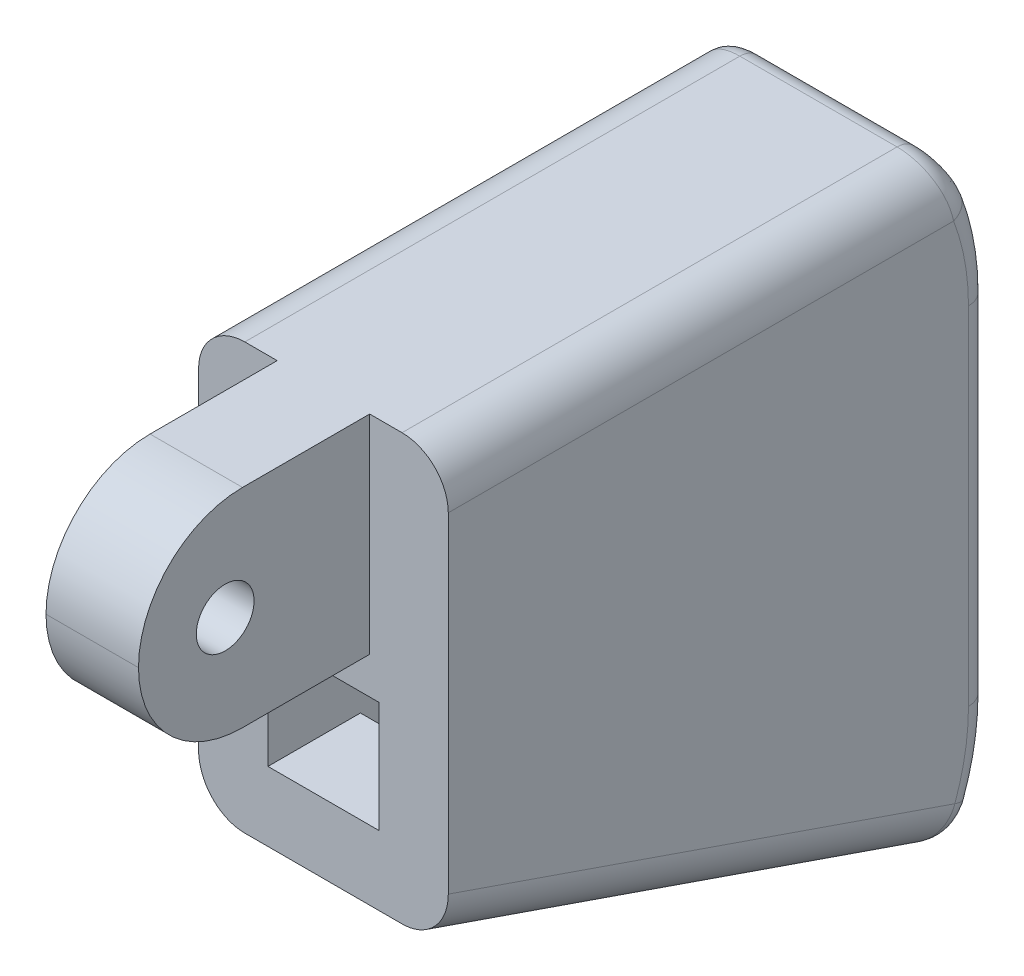
SolidWorks part; units mm, degrees
ref_plane "Front Plane" through (0, 0, 0) normal (0, 0, 1) x (1, 0, 0)
ref_plane "Top Plane" through (0, 0, 0) normal (0, 1, 0) x (1, 0, 0)
ref_plane "Right Plane" through (0, 0, 0) normal (1, 0, 0) x (0, 0, -1)
sketch "Sketch1" plane through (0, 0, 0) normal (0, 0, 1) x (1, 0, 0)
  line L1 (-2.4, -10) -> (2.4, -10)
  line L2 (-2.4, -10) -> (-2.4, 10)
  line L3 (-2.4, 10) -> (2.4, 10)
  line L4 (2.4, -10) -> (2.4, 10)
  line L5 (-2.4, -10) -> (2.4, 10) construction
  line L6 (-2.4, 10) -> (2.4, -10) construction
  line L7 (-5.4, -13) -> (5.4, -13)
  line L8 (-5.4, -13) -> (-5.4, 13)
  line L9 (-5.4, 13) -> (5.4, 13)
  line L10 (5.4, -13) -> (5.4, 13)
  line L11 (-5.4, -13) -> (5.4, 13) construction
  line L12 (-5.4, 13) -> (5.4, -13) construction
  line L13 (-2.4, 2.4) -> (2.4, 2.4)
  line L14 (-2.4, 2.4) -> (-2.4, -2.4)
  line L15 (-2.4, -2.4) -> (2.4, -2.4)
  line L16 (2.4, 2.4) -> (2.4, -2.4)
  line L17 (-2.4, 2.4) -> (2.4, -2.4) construction
  line L18 (-2.4, -2.4) -> (2.4, 2.4) construction
  point P0 (0, 0)
  point P6 (0, 0)
  point P11 (0, 0)
  dimension "D1" = 4.8
  dimension "D2" = 20
  dimension "D3" = 26
  dimension "D4" = 10.8
  dimension "D5" = 4.8
extrude "Boss-Extrude1" add sketch "Sketch1" along normal blind 18 contours L7 L10 L9 L8 L4 L1 L2 L3 region at (-5.1185, 0, 0)
sketch "Sketch2" plane through (0, 0, 18) normal (0, 0, 1) x (1, 0, 0)
  line L0 (2.4, -10) -> (2.4, 10) construction
  line L1 (-2.4, 2.4) -> (2.4, 2.4)
  line L2 (-2.4, 2.4) -> (-2.4, -2.4)
  line L3 (-2.4, -2.4) -> (2.4, -2.4)
  line L4 (2.4, 2.4) -> (2.4, -2.4)
  line L5 (-2.4, 2.4) -> (2.4, -2.4) construction
  line L6 (-2.4, -2.4) -> (2.4, 2.4) construction
  line L8 (-5.4, -13) -> (5.4, -13)
  line L9 (-5.4, -13) -> (-5.4, 13)
  line L10 (-5.4, 13) -> (5.4, 13)
  line L11 (5.4, -13) -> (5.4, 13)
  line L12 (-5.4, -13) -> (5.4, 13) construction
  line L13 (-5.4, 13) -> (5.4, -13) construction
  point P1 (0, 0)
  point P8 (0, 0)
  dimension "D1" = 4.8
extrude "Boss-Extrude2" add sketch "Sketch2" along normal blind 4
sketch "Sketch5" plane through (0, 0, 22) normal (0, 0, 1) x (1, 0, 0)
  line L1 (5.4, 13) -> (-5.4, 13) construction
  line L2 (-2, 4) -> (2, 4)
  line L3 (-2, 4) -> (-2, 13)
  line L4 (-2, 13) -> (2, 13)
  line L5 (2, 4) -> (2, 13)
  line L6 (-2, 4) -> (2, 13) construction
  line L8 (-2, 13) -> (2, 4) construction
  line L9 (-5.4, 13) -> (-5.4, -13) construction
  point P0 (0, 8.5)
  dimension "D1" = 9
  dimension "D2" = 4
  dimension "D3" = 5.4
extrude "Boss-Extrude3" add sketch "Sketch5" along normal blind 10
fillet "Fillet2" radius 4.5 2 edges at (0, 13, 32) (0, 4, 32)
hole_wizard "Tap Drill for M3x0.5 Tap1" positions "3DSketch1" profile "Sketch7" hole size "M3x0.5" standard "ANSI Metric"
sketch3d "3DSketch1"
  line L0 (-2, 13, 27.5) -> (-2, 13, 22) construction
  point P0 (-2, 8.5027, 28.25)
  dimension "D1" = 3.75
  dimension "D2" = 4.4973
sketch "Sketch7" plane through (-2, 8.5027, 28.25) normal (0, 1, 0) x (0, 0, 1)
  line L0 (0, 0) -> (0, 4.7511)
  line L1 (0, 4.7511) -> (1.25, 4)
  line L2 (1.25, 4) -> (1.25, 0)
  line L5 (1.25, 0) -> (0, 0)
  line L10 (0, 4.7511) -> (-1.25, 4) construction
  line L11 (0, -6.35) -> (0, 107.95) construction
  dimension "Hole Dia." = 2.5
  dimension "Hole Depth" = 4
  dimension "Drill Angle" = 118
fillet "Fillet1" [suppressed] radius 3
sketch "Sketch8" plane through (5.4, 0, 0) normal (1, 0, 0) x (0, 0, -1)
  line L0 (-22, -2.4) -> (-22, -13)
  line L1 (-22, -13) -> (-22, 13) construction
  line L2 (-22, -13) -> (0, -13)
  line L3 (0, -13) -> (-22, -2.4)
extrude "Cut-Extrude2" cut sketch "Sketch8" against normal through all
sketch "Sketch9" plane through (5.4, 0, 0) normal (1, 0, 0) x (0, 0, -1)
  line L0 (-22, -2.4) -> (0, -13)
  line L2 (0, -13) -> (-22, -5.4)
  line L3 (-22, -5.4) -> (-22, -2.4)
  dimension "D1" = 3
extrude "Boss-Extrude5" add sketch "Sketch9" against normal up to surface (10.8 mm away) up to face at (-5.4, 0.725, 13.75)
sketch "Sketch10" plane through (5.4, 0, 0) normal (1, 0, 0) x (0, 0, -1)
  line L0 (0, 13) -> (0, -13)
  line L1 (1.5, 7.5) -> (1.5, -7.5)
  arc A0 (0, 13) -> (1.5, 7.5) centre (-9.3333, 7.5) cw
  arc A1 (0, -13) -> (1.5, -7.5) centre (-9.3333, -7.5) ccw
  point P7 (1.5, 0)
  point P8 (0, 0)
  dimension "D1" = 1.5
  dimension "D2" = 15
extrude "Boss-Extrude6" add sketch "Sketch10" against normal up to surface (10.8 mm away) up to face at (-5.4, -0.4, 13.75)
sketch "Sketch11" plane through (0, 0, 0) normal (0, 0, 1) x (1, 0, 0)
  line L0 (2.4, 10) -> (-2.4, 10)
  line L1 (-2.4, 10) -> (-2.4, -10)
  line L2 (-2.4, -10) -> (2.4, -10)
  line L3 (2.4, -10) -> (2.4, 10)
extrude "Cut-Extrude3" cut sketch "Sketch11" against normal blind 10
fillet "Fillet3" radius 2 4 edges at (5.4, -9.2, 11) (5.4, 13, 11) (-5.4, 13, 11)
fillet "Fillet5" radius 1 12 edges at (5.4, -9.3678, -1.3378) (4.9705, -12.3214, -0.368) (-4.6349, -12.6219, -0.2127) (-5.4, 0, -1.5) (-5.4, 9.2739, -1.3538) (-4.9104, 12.311, -0.3731) (0, 13, 0) (4.533, 12.6481, -0.1986) (5.4, 9.2739, -1.3538) (5.4, 0, -1.5)
